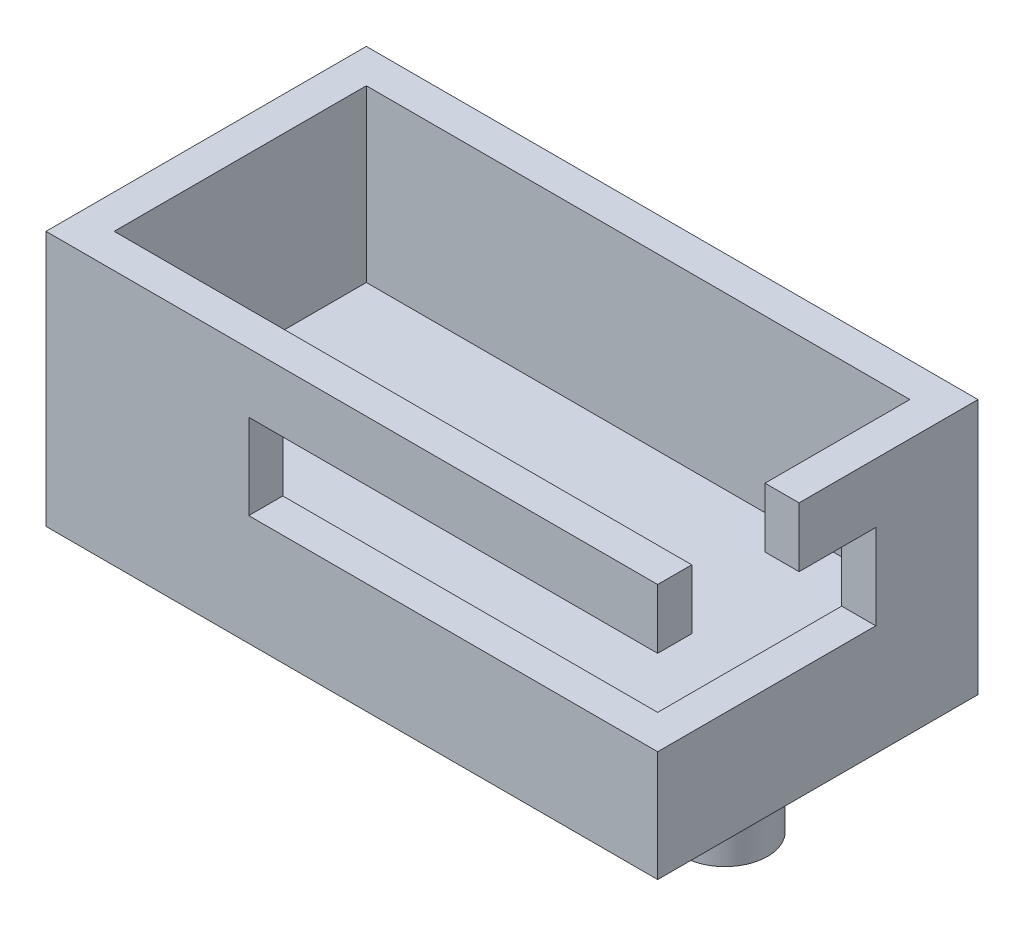
SolidWorks part; units mm, degrees
ref_plane "Front Plane" through (0, 0, 0) normal (0, 0, 1) x (1, 0, 0)
ref_plane "Top Plane" through (0, 0, 0) normal (0, 1, 0) x (1, 0, 0)
ref_plane "Right Plane" through (0, 0, 0) normal (1, 0, 0) x (0, 0, -1)
sketch "Sketch1" plane through (0, 0, 0) normal (0, 1, 0) x (1, 0, 0)
  line L0 (-2, -2) -> (-2, 16.8)
  line L1 (0, 0) -> (31.9, 0)
  line L2 (0, 0) -> (0, 14.8)
  line L3 (0, 14.8) -> (31.9, 14.8)
  line L4 (31.9, 0) -> (31.9, 14.8)
  line L5 (-2, 16.8) -> (33.9, 16.8)
  line L6 (33.9, -2) -> (33.9, 16.8)
  line L7 (-2, -2) -> (33.9, -2)
  dimension "D1" = 14.8
  dimension "D2" = 31.9
  dimension "D3" = 2
extrude "Boss-Extrude1" add sketch "Sketch1" along normal blind 10
extrude "Boss-Extrude2" add sketch "Sketch1<2>" against normal blind 5 contours L0 L7 L6 L5 L4 L1 L2 L3 | L1 L4 L3 L2 region at (-1.5948, 0, -7.4) region at (15.95, 0, -7.4)
sketch "Sketch1<2>" plane through (0, 0, 0) normal (0, 1, 0) x (1, 0, 0) same geometry as "Sketch1"
sketch "Sketch2" plane through (0, 0, 2) normal (0, 0, 1) x (1, 0, 0)
  line L0 (33.9, 10) -> (33.9, -5) construction
  line L1 (9.9, 6.5) -> (33.9, 6.5)
  line L2 (9.9, 6.5) -> (9.9, 1.5)
  line L3 (9.9, 1.5) -> (33.9, 1.5)
  line L4 (33.9, 6.5) -> (33.9, 1.5)
  line L5 (-2, -5) -> (33.9, -5) construction
  dimension "D1" = 24
  dimension "D2" = 5
  dimension "D3" = 6.5
extrude "Cut-Extrude1" cut sketch "Sketch2" against normal offset from surface (12.8 mm away) 6 up to face at (15.95, 2.5, -16.8)
sketch "Sketch3" plane through (33.9, 0, 0) normal (1, 0, 0) x (0, 0, -1)
  line L0 (-2, 10) -> (16.8, 10) construction
  line L1 (0, 6.5) -> (6.3, 6.5)
  line L2 (0, 6.5) -> (0, 10)
  line L3 (0, 10) -> (6.3, 10)
  line L4 (6.3, 6.5) -> (6.3, 10)
  dimension "D1" = 6.3
extrude "Cut-Extrude2" cut sketch "Sketch3" against normal up to surface (2 mm away) up to face at (31.9, 4.5, -6.4)
sketch "Sketch4" plane through (0, -5, 0) normal (0, -1, 0) x (1, 0, 0)
  line L0 (15.95, 2) -> (15.95, -16.8) construction
  line L1 (-2, 2) -> (33.9, 2) construction
  line L2 (-2, -16.8) -> (33.9, -16.8) construction
  line L3 (3.45, -7.4) -> (15.95, -7.4) construction
  circle A0 centre (3.45, -7.4) radius 2.5
  circle A1 centre (28.45, -7.4) radius 2.5
  dimension "D1" = 5
  dimension "D2" = 12.5
extrude "Boss-Extrude3" add sketch "Sketch4" along normal blind 5
fillet "Fillet1" radius 0.4 2 edges at (28.45, -5, -4.9) (3.45, -5, -4.9)
